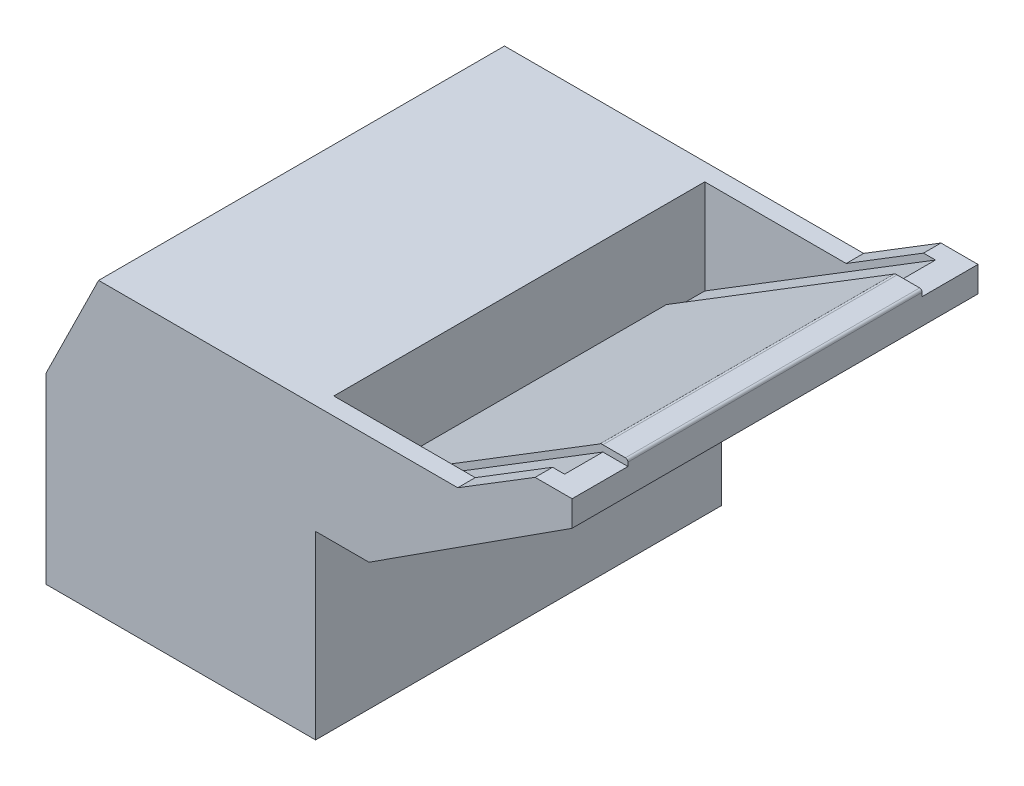
SolidWorks part; units mm, degrees
ref_plane "Front Plane" through (0, 0, 0) normal (0, 0, 1) x (1, 0, 0)
ref_plane "Top Plane" through (0, 0, 0) normal (0, 1, 0) x (1, 0, 0)
ref_plane "Right Plane" through (0, 0, 0) normal (1, 0, 0) x (0, 0, -1)
sketch "Sketch2" plane through (0, 0, 0) normal (0, 0, 1) x (1, 0, 0)
  line L0 (-170.2771, 41.1047) -> (417.0562, 41.1047) construction
  line L1 (1737.3459, 48.7127) -> (1737.3459, 1466.5786)
  line L2 (1755.8876, 2332.5208) -> (2867.8622, 2332.5208)
  line L3 (2867.8622, 2332.5208) -> (3482.8331, 2711.3987)
  line L4 (3482.8331, 2711.3987) -> (3777.2482, 2711.3987)
  line L5 (3777.2482, 2711.3987) -> (3777.2482, 2507.9456)
  line L6 (3777.2482, 2507.9456) -> (2162.0532, 1466.5786)
  line L7 (2162.0532, 1466.5786) -> (1737.3459, 1466.5786)
  line L8 (1755.8876, 2332.5208) -> (11.5642, 2332.5208)
  line L9 (11.5642, 2332.5208) -> (-406.7577, 1483.9438)
  line L10 (-406.7577, 1483.9438) -> (-406.7577, 29.9176)
  line L11 (-406.7577, 29.9176) -> (1737.3459, 29.9176)
  line L12 (1737.3459, 29.9176) -> (1737.3459, 48.7127)
extrude "Boss-Extrude1" add sketch "Sketch2" along normal blind 3050
sketch "Sketch3" plane through (0, 0, 3050) normal (0, 0, 1) x (1, 0, 0)
  line L0 (1743.2808, 1580.9491) -> (1743.2808, 2332.5208)
  line L1 (2867.8622, 2332.5208) -> (11.5642, 2332.5208) construction
  line L2 (3578.156, 2711.3987) -> (1743.2808, 1580.9491)
  line L3 (3777.2482, 2711.3987) -> (3482.8331, 2711.3987) construction
  line L4 (3482.8331, 2711.3987) -> (2867.8622, 2332.5208) construction
  line L5 (1743.2808, 2332.5208) -> (2867.8622, 2332.5208)
  line L6 (2867.8622, 2332.5208) -> (3482.8331, 2711.3987)
  line L7 (3482.8331, 2711.3987) -> (3578.156, 2711.3987)
  dimension "D1" = 50
extrude "Cut-Extrude1" cut sketch "Sketch3" against normal blind 2950 from offset 50 offset against normal yes
sketch "Sketch5" plane through (-226.386, 367.4557, 0) normal (-0.5245, 0.8514, 0) x (0.8514, 0.5245, 0)
  line L0 (2707.6966, -355) -> (4468.6249, -355)
  line L1 (2707.6966, -50) -> (2707.6966, -3000) construction
  line L2 (4468.6249, -50) -> (4468.6249, -3000) construction
  line L3 (4468.6249, -355) -> (4468.6249, -2695)
  line L4 (4468.6249, -2695) -> (2707.6966, -2695)
  line L6 (2313.4722, -3000) -> (4468.6249, -3000) construction
  line L7 (4387.468, -50) -> (3665.1539, -50) construction
  line L8 (2707.6966, -2695) -> (2313.4722, -2695)
  line L9 (2313.4722, -50) -> (2313.4722, -3000) construction
  line L10 (2313.4722, -2695) -> (2313.4722, -355)
  line L11 (2313.4722, -355) -> (2707.6966, -355)
  dimension "D1" = 305
  dimension "D2" = 305
extrude "Boss-Extrude2" add sketch "Sketch5" along normal blind 50
extrude "Boss-Extrude3" add sketch "Sketch2<2>" against normal blind 89
sketch "Sketch2<2>" plane through (0, 0, 0) normal (0, 0, 1) x (1, 0, 0) same geometry as "Sketch2"
extrude "Boss-Extrude4" add sketch "Sketch2<3>" along normal blind 89 from offset 3050
sketch "Sketch2<3>" plane through (0, 0, 0) normal (0, 0, 1) x (1, 0, 0) same geometry as "Sketch2"
sketch "Sketch6" plane through (0, 2711.3987, 0) normal (0, 1, 0) x (1, 0, 0)
  line L0 (3578.156, -355) -> (3777.2482, -355)
  line L1 (3777.2482, -3139) -> (3777.2482, 89) construction
  line L2 (3777.2482, -355) -> (3777.2482, -2695)
  line L3 (3777.2482, -2695) -> (3578.156, -2695)
  line L4 (3578.156, -2695) -> (3578.156, -355)
extrude "Boss-Extrude5" add sketch "Sketch6" along normal blind 50
sketch "Sketch7" plane through (0, 0, 2695) normal (0, 0, 1) x (1, 0, 0)
  line L0 (3551.9293, 2753.9682) -> (3578.156, 2711.3987)
  line L1 (3578.156, 2711.3987) -> (3578.156, 2761.3987)
  line L2 (3578.156, 2761.3987) -> (3578.156, 2711.3987) construction
  arc A0 (3578.156, 2761.3987) -> (3551.9293, 2753.9682) centre (3571.073, 2736.3987) ccw
extrude "Boss-Extrude6" add sketch "Sketch7" against normal up to vertex (2340 mm away) up to point (1743.2808, 1639.6766, 355)
fillet "Fillet1" radius 20 1 edges at (3777.2482, 2761.3987, 1525)
